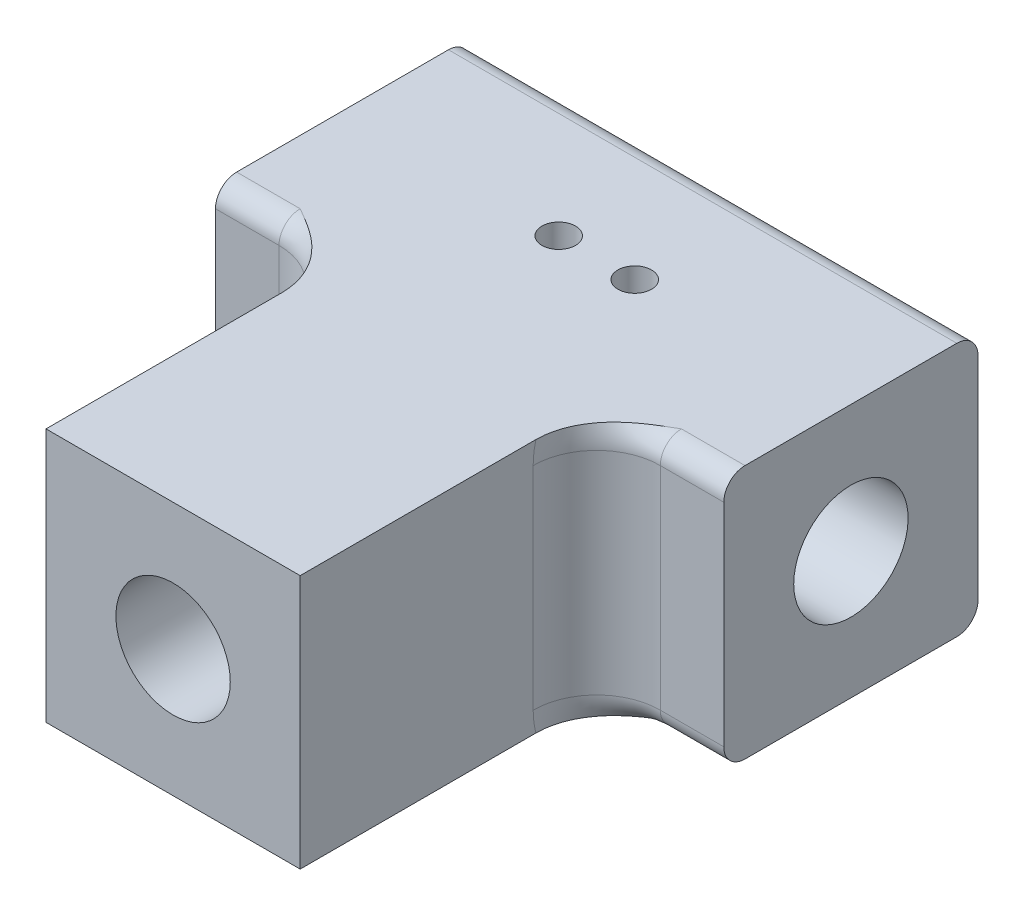
SolidWorks part; units mm, degrees
ref_plane "Front Plane" through (0, 0, 0) normal (0, 0, 1) x (1, 0, 0)
ref_plane "Top Plane" through (0, 0, 0) normal (0, 1, 0) x (1, 0, 0)
ref_plane "Right Plane" through (0, 0, 0) normal (1, 0, 0) x (0, 0, -1)
sketch "Sketch1" plane through (0, 0, 0) normal (0, 1, 0) x (1, 0, 0)
  line L3 (-6, -3) -> (6, -3)
  line L4 (-6, -3) -> (-6, 3)
  line L5 (-6, 3) -> (6, 3)
  line L6 (6, -3) -> (6, 3)
  line L7 (-6, -3) -> (6, 3) construction
  line L8 (-6, 3) -> (6, -3) construction
  point P0 (0, 0)
  dimension "D1" = 12
  dimension "D2" = 6
extrude "Boss-Extrude1" add sketch "Sketch1" along normal blind 6
sketch "Sketch2" plane through (0, 6, 0) normal (0, 1, 0) x (1, 0, 0)
  line L0 (-3.3, 0) -> (3.3, 0) construction
  line L1 (0.8969, 0) -> (-0.8969, 0)
  line L2 (0, -3.3) -> (0, 3.3) construction
  point P0 (0.8969, 0)
  point P1 (-0.8969, 0)
  point P7 (0, 0)
  dimension "D1" = 1.7937
sketch "Sketch6" plane through (-6, 0, 0) normal (-1, 0, 0) x (0, 0, 1)
  line L0 (0, -55) -> (0, 55) construction
  line L1 (-3, 6) -> (3, 6) construction
  point P0 (0, 4.5)
  dimension "D1" = 1.5
hole_wizard "1/32 (0.03125) Diameter Hole1" positions "Sketch9" profile "Sketch10" hole size "1/32" standard "ANSI Inch" end condition through all
sketch "Sketch9" plane through (0, 6, 0) normal (0, 1, 0) x (1, 0, 0)
  point P0 (0.8969, 0)
  point P3 (-0.8969, 0)
sketch "Sketch10" plane through (0.8969, 6, 0) normal (1, 0, 0) x (0, 0, 1)
  line L0 (0, 0) -> (0, 6)
  line L1 (0, 6) -> (0.3969, 6)
  line L2 (0.3969, 6) -> (0.3969, 0)
  line L5 (0.3969, 0) -> (0, 0)
  line L11 (0, -6.35) -> (0, 107.95) construction
  dimension "Thru Hole Dia." = 0.7937
  dimension "Thru Hole Depth" = 6
hole_wizard "Tap Drill for M2x0.4 Tap1" [suppressed] positions "Sketch7" profile "Sketch8" hole size "M2x0.4" standard "ANSI Metric"
sketch "Sketch7" [suppressed] plane through (-5, 0, 0) normal (-1, 0, 0) x (0, 0, 1)
  point P0 (0, 1.5)
sketch "Sketch8" [suppressed] plane through (-5, 1.5, 0) normal (0, 1, 0) x (0, 0, 1)
  line L0 (0, 0) -> (0, 4.85)
  line L1 (0, 4.85) -> (0.8, 4.3693)
  line L2 (0.8, 4.3693) -> (0.8, 0)
  line L5 (0.8, 0) -> (0, 0)
  line L10 (0, 4.85) -> (-0.8, 4.3693) construction
  line L11 (0, -6.35) -> (0, 107.95) construction
  dimension "Hole Dia." = 1.6
  dimension "Hole Depth" = 4.85
  dimension "Drill Angle" = 118
mirror "Mirror1" [suppressed] about plane through (0, 0, 0) normal (1, 0, 0)
sketch "Sketch15" plane through (0, 0, 3) normal (0, 0, 1) x (1, 0, 0)
  line L0 (0, -3.3) -> (0, 3.3) construction
  line L1 (-3, 0) -> (3, 0)
  line L2 (-3, 0) -> (-3, 6)
  line L3 (-3, 6) -> (3, 6)
  line L4 (3, 0) -> (3, 6)
  line L5 (-3, 0) -> (3, 6) construction
  line L6 (-3, 6) -> (3, 0) construction
  line L7 (-6, 6) -> (6, 6) construction
  point P0 (0, 3)
  dimension "D1" = 6
  dimension "D2" = 6
extrude "Boss-Extrude2" add sketch "Sketch15" along normal blind 7
sketch "Sketch16" plane through (0, 0, 10) normal (0, 0, 1) x (1, 0, 0)
  line L0 (0, -3.3) -> (0, 3.3) construction
  line L1 (3, 6) -> (-3, 6) construction
  circle A0 centre (0, 3) radius 1.35
  point P0 (0, 3)
  dimension "D2" = 2.7
  dimension "D1" = 3
hole_wizard "M2x0.4 Tapped Hole1" [suppressed] positions "Sketch17" profile "Sketch18" tap size "M2x0.4" standard "ANSI Metric"
sketch "Sketch17" [suppressed] plane through (0, 0, 8.5) normal (0, 0, 1) x (1, 0, 0)
  point P0 (0, 1.5)
sketch "Sketch18" [suppressed] plane through (0, 1.5, 8.5) normal (1, 0, 0) x (0, -1, 0)
  line L0 (0, 0) -> (0, 5.4807)
  line L1 (0, 5.4807) -> (0.8, 5)
  line L2 (0.8, 5) -> (0.8, 0)
  line L5 (0.8, 0) -> (0, 0)
  line L10 (0, 5.4807) -> (-0.8, 5) construction
  line L11 (0, -6.35) -> (0, 107.95) construction
  dimension "Tap Drill Dia." = 1.6
  dimension "Tap Drill Depth" = 5
  dimension "Drill Angle" = 118
cosmetic thread "Hole Thread1" [suppressed] parameters "D1"=4, "D2"=2
fillet "Fillet4" radius 0.5 6 edges at (4.5, 6, 3) (4.5, 0, 3) (-4.5, 0, 3) (0, 0, -3) (0, 6, -3) (-4.5, 6, 3)
fillet "Fillet3" radius 1.5 6 edges at (-3, 3, 3) (3, 3, 3) (-3, 5.8536, 2.8536) (-3, 0.1464, 2.8536) (3, 0.1464, 2.8536) (3, 5.8536, 2.8536)
sketch "Sketch19" plane through (-6, 0, 0) normal (-1, 0, 0) x (0, 0, 1)
  line L0 (0, -3.3) -> (0, 3.3) construction
  line L1 (-2.5, 6) -> (2.5, 6) construction
  circle A0 centre (0, 3) radius 1.35
  dimension "D1" = 2.7
  dimension "D2" = 3
extrude "Cut-Extrude1" cut sketch "Sketch19" against normal blind 5.5 contours A0
extrude "Cut-Extrude2" cut sketch "Sketch16" against normal blind 5 contours A0
mirror "Mirror2" about plane through (0, 0, 0) normal (1, 0, 0) of "Cut-Extrude1"
